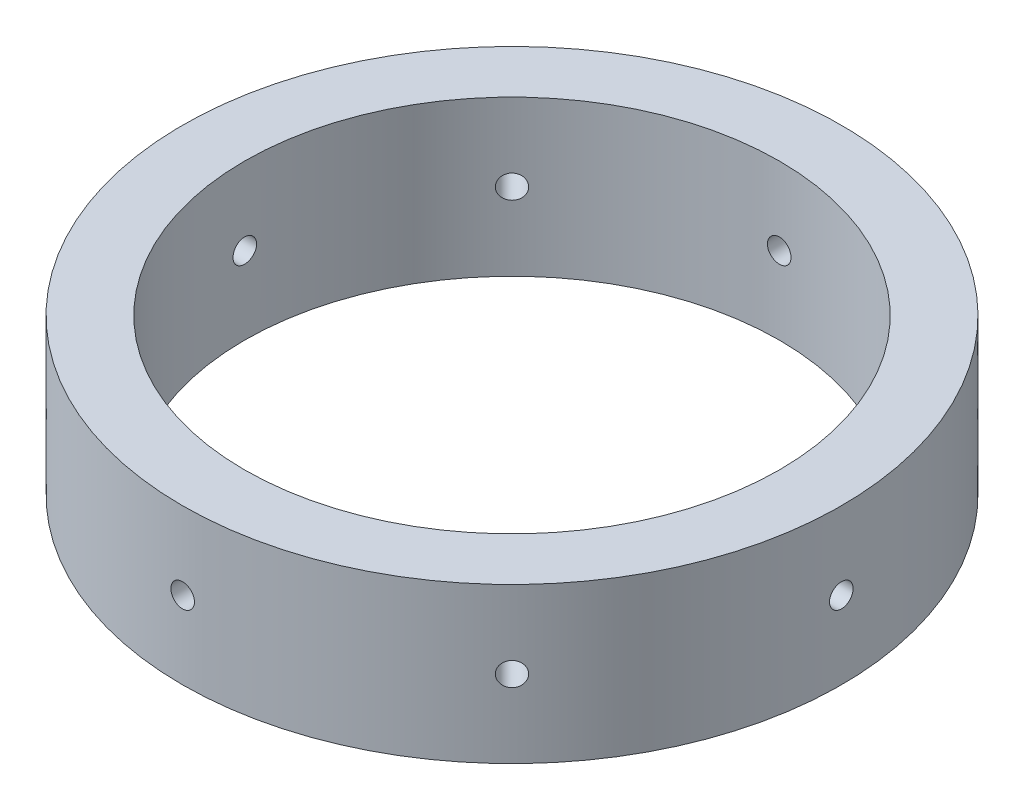
SolidWorks part; units mm, degrees
ref_plane "Front Plane" through (0, 0, 0) normal (0, 0, 1) x (1, 0, 0)
ref_plane "Top Plane" through (0, 0, 0) normal (0, 1, 0) x (1, 0, 0)
ref_plane "Right Plane" through (0, 0, 0) normal (1, 0, 0) x (0, 0, -1)
sketch "Sketch3" plane through (0, 0, 0) normal (0, 1, 0) x (1, 0, 0)
  circle A0 centre (0, 0) radius 53.1
  circle A1 centre (0, 0) radius 43.1
  dimension "D1" = 106.2
  dimension "D2" = 86.2
extrude "Boss-Extrude1" add sketch "Sketch3" along normal blind 25
ref_plane "Plane2" through (53.1, 0, 0) normal (1, 0, 0) x (0, 0, -1)
sketch "Sketch5" plane through (53.1, 0, 0) normal (1, 0, 0) x (0, 0, -1)
  line L0 (0, 0) -> (0, 25) construction
  line L1 (43.1, 25) -> (-43.1, 25) construction
  line L2 (-55.8566, 10) -> (-56.1948, 10) construction
  line L3 (-56.1948, 10) -> (55.6312, 10) construction
  circle A0 centre (0, 12.5) radius 1.9
  dimension "D1" = 3.8
extrude "Cut-Extrude1" cut sketch "Sketch5" against normal up to next
pattern_circular "CirPattern1" count 8 over 360 about axis through (0, 25, 0) along (0, -1, 0) of "Cut-Extrude1" reverse direction yes
equation "\"circulo grande\" = 106.2mm"
equation "\"D1@Sketch3\"=\"circulo grande\""
equation "\"circulo pequeño\" = 86.20mm"
equation "\"D2@Sketch3\"=\"circulo pequeño\""
equation "\"ancho\"= 2.5cm"
equation "\"Boss-Extrude1@Boss-Extrude1\"=\"ancho\""
equation "\"circulo tornillo\" = 3.8mm"
equation "\"D1@Sketch5\"=\"circulo tornillo\""
